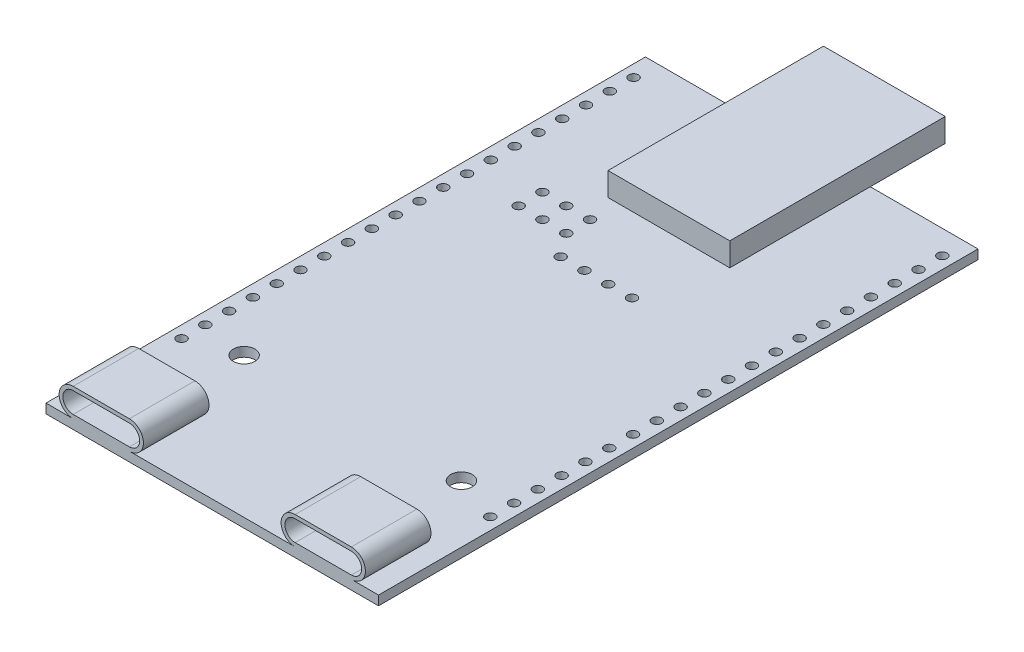
SolidWorks part; units mm, degrees
ref_plane "Piano frontale" through (0, 0, 0) normal (0, 0, 1) x (1, 0, 0)
ref_plane "Piano superiore" through (0, 0, 0) normal (0, 1, 0) x (1, 0, 0)
ref_plane "Piano destro" through (0, 0, 0) normal (1, 0, 0) x (0, 0, -1)
sketch "Schizzo1" plane through (0, 0, 0) normal (0, 1, 0) x (1, 0, 0)
  line L1 (0, 0) -> (-35.5, 0)
  line L2 (0, 0) -> (0, 64)
  line L3 (0, 64) -> (-35.5, 64)
  line L4 (-35.5, 0) -> (-35.5, 64)
  dimension "D1" = 64
  dimension "D2" = 35.5
extrude "Estrusione-Estrusione1" add sketch "Schizzo1" along normal blind 1
sketch "Schizzo2" plane through (0, 1, 0) normal (0, 1, 0) x (1, 0, 0)
  line L0 (0, 64) -> (-35.5, 64) construction
  line L1 (-11.5, 49) -> (-24.5, 49)
  line L2 (-11.5, 49) -> (-11.5, 72)
  line L3 (-11.5, 72) -> (-24.5, 72)
  line L4 (-24.5, 49) -> (-24.5, 72)
  line L5 (-35.5, 64) -> (-35.5, 0) construction
  dimension "D1" = 13
  dimension "D2" = 23
  dimension "D3" = 8
  dimension "D4" = 11
extrude "Estrusione-Estrusione2" add sketch "Schizzo2" along normal blind 2.5
sketch "Schizzo3" plane through (0, 1, 0) normal (0, 1, 0) x (1, 0, 0)
  line L0 (0, 64) -> (-11.5, 64) construction
  line L1 (0, 0) -> (0, 64) construction
  line L2 (-35.5, 64) -> (-35.5, 0) construction
  line L3 (-21.56, 41) -> (-13.94, 41) construction
  line L4 (-35.5, 0) -> (0, 0) construction
  line L5 (-28.5, 43.46) -> (-23.42, 43.46) construction
  line L6 (-23.42, 43.46) -> (-23.42, 46) construction
  line L7 (-23.42, 46) -> (-28.5, 46) construction
  line L8 (-28.5, 46) -> (-28.5, 43.46) construction
  line L9 (-24.5, 64) -> (-35.5, 64) construction
  circle A0 centre (-1.27, 61.46) radius 0.51
  circle A1 centre (-1.27, 58.92) radius 0.51
  circle A2 centre (-1.27, 56.38) radius 0.51
  circle A3 centre (-1.27, 53.84) radius 0.51
  circle A4 centre (-1.27, 51.3) radius 0.51
  circle A5 centre (-1.27, 48.76) radius 0.51
  circle A6 centre (-1.27, 46.22) radius 0.51
  circle A7 centre (-1.27, 43.68) radius 0.51
  circle A8 centre (-1.27, 41.14) radius 0.51
  circle A9 centre (-1.27, 38.6) radius 0.51
  circle A10 centre (-1.27, 36.06) radius 0.51
  circle A11 centre (-1.27, 33.52) radius 0.51
  circle A12 centre (-1.27, 30.98) radius 0.51
  circle A13 centre (-1.27, 28.44) radius 0.51
  circle A14 centre (-1.27, 25.9) radius 0.51
  circle A15 centre (-1.27, 23.36) radius 0.51
  circle A16 centre (-1.27, 20.82) radius 0.51
  circle A17 centre (-1.27, 18.28) radius 0.51
  circle A18 centre (-1.27, 15.74) radius 0.51
  circle A19 centre (-1.27, 13.2) radius 0.51
  circle A20 centre (-34.23, 61.46) radius 0.51
  circle A21 centre (-34.23, 58.92) radius 0.51
  circle A22 centre (-34.23, 56.38) radius 0.51
  circle A23 centre (-34.23, 53.84) radius 0.51
  circle A24 centre (-34.23, 51.3) radius 0.51
  circle A25 centre (-34.23, 48.76) radius 0.51
  circle A26 centre (-34.23, 46.22) radius 0.51
  circle A27 centre (-34.23, 43.68) radius 0.51
  circle A28 centre (-34.23, 41.14) radius 0.51
  circle A29 centre (-34.23, 38.6) radius 0.51
  circle A30 centre (-34.23, 36.06) radius 0.51
  circle A31 centre (-34.23, 33.52) radius 0.51
  circle A32 centre (-34.23, 30.98) radius 0.51
  circle A33 centre (-34.23, 28.44) radius 0.51
  circle A34 centre (-34.23, 25.9) radius 0.51
  circle A35 centre (-34.23, 23.36) radius 0.51
  circle A36 centre (-34.23, 20.82) radius 0.51
  circle A37 centre (-34.23, 18.28) radius 0.51
  circle A38 centre (-34.23, 15.74) radius 0.51
  circle A39 centre (-34.23, 13.2) radius 0.51
  circle A40 centre (-21.56, 41) radius 0.51
  circle A41 centre (-19.02, 41) radius 0.51
  circle A42 centre (-16.48, 41) radius 0.51
  circle A43 centre (-13.94, 41) radius 0.51
  circle A44 centre (-28.5, 46) radius 0.51
  circle A45 centre (-25.96, 46) radius 0.51
  circle A46 centre (-23.42, 46) radius 0.51
  circle A47 centre (-28.5, 43.46) radius 0.51
  circle A48 centre (-25.96, 43.46) radius 0.51
  circle A49 centre (-23.42, 43.46) radius 0.51
  point P108 (-26.9595, 44.1376)
  point P109 (-26.9595, 45.7828)
  dimension "D1" = 1.02
  dimension "D3" = 2.54
  dimension "D4" = 1.27
  dimension "D8" = 2.54
  dimension "D9" = 2.54
  dimension "D10" = 2.54
  dimension "D5" = 2.54
  dimension "D7" = 1.27
  dimension "D11" = 13.94
  dimension "D12" = 41
  dimension "D13" = 2.54
  dimension "D14" = 2.54
  dimension "D15" = 7
  dimension "D16" = 18
  dimension "D2" = 20
  dimension "D6" = 2
extrude "Taglio-Estrusione1" cut sketch "Schizzo3" against normal blind 2.5
sketch "Schizzo6" plane through (0, 0, 0) normal (0, 0, 1) x (1, 0, 0)
  line L0 (-32.6, 2.5) -> (-26.6, 2.5) construction
  line L1 (-32.6, 4) -> (-26.6, 4)
  line L2 (-32.6, 1) -> (-26.6, 1)
  line L3 (-34.1, 2.5) -> (-25.1, 2.5) construction
  line L4 (-35.5, 1) -> (0, 1) construction
  line L5 (-8.9, 2.5) -> (-2.9, 2.5) construction
  line L6 (-8.9, 4) -> (-2.9, 4)
  line L7 (-8.9, 1) -> (-2.9, 1)
  line L8 (0, 1) -> (0, 0) construction
  line L9 (-32.6, 2.5) -> (-26.6, 2.5) construction
  line L10 (-32.6, 3.6) -> (-26.6, 3.6)
  line L11 (-32.6, 1.4) -> (-26.6, 1.4)
  line L12 (-8.9, 2.5) -> (-2.9, 2.5) construction
  line L13 (-8.9, 3.6) -> (-2.9, 3.6)
  line L14 (-8.9, 1.4) -> (-2.9, 1.4)
  arc A0 (-32.6, 4) -> (-32.6, 1) centre (-32.6, 2.5) ccw
  arc A1 (-26.6, 1) -> (-26.6, 4) centre (-26.6, 2.5) ccw
  arc A2 (-8.9, 4) -> (-8.9, 1) centre (-8.9, 2.5) ccw
  arc A3 (-2.9, 1) -> (-2.9, 4) centre (-2.9, 2.5) ccw
  arc A4 (-32.6, 3.6) -> (-32.6, 1.4) centre (-32.6, 2.5) ccw
  arc A5 (-26.6, 1.4) -> (-26.6, 3.6) centre (-26.6, 2.5) ccw
  arc A6 (-8.9, 3.6) -> (-8.9, 1.4) centre (-8.9, 2.5) ccw
  arc A7 (-2.9, 1.4) -> (-2.9, 3.6) centre (-2.9, 2.5) ccw
  point P2 (-29.6, 2.5)
  point P14 (-5.9, 2.5)
  point P19 (-1.4, 2.5)
  point P25 (-29.6, 2.5)
  point P30 (-5.9, 2.5)
  line M21 (0, 1) -> (-35.5, 1)
  dimension "D1" = 9
  dimension "D2" = 3
  dimension "D3" = 1.4
  dimension "D4" = 1.4
  dimension "D5" = 0.4
extrude "Estrusione-Estrusione3" add sketch "Schizzo6" against normal blind 7 contours L11 A5 L10 A4 | A1 L1 A0 A5 L11 A4 L10 M21 | L14 A7 L13 A6 | A3 L6 A2 A7 L14 A6 L13 M21 region at (-10.3051, 2.5, 0) region at (-29.6, 3.9051, 0) region at (-29.6, 2.5, 0) region at (-5.9, 2.5, 0)
extrude "Taglio-Estrusione2" cut sketch "Schizzo6<3>" against normal blind 6 contours L11 A5 L10 A4 | L14 A7 L13 A6 region at (-29.6, 2.5, 0) region at (-5.9, 2.5, 0)
sketch "Schizzo6<3>" plane through (0, 0, 0) normal (0, 0, 1) x (1, 0, 0) same geometry as "Schizzo6"
sketch "Schizzo7" plane through (0, 1, 0) normal (0, 1, 0) x (1, 0, 0)
  line L0 (0, 0) -> (0, 64) construction
  line L1 (-35.5, 64) -> (-35.5, 0) construction
  line L2 (-26.6, 0) -> (-8.9, 0) construction
  circle A0 centre (-29.35, 15) radius 1.15
  circle A1 centre (-6.15, 15) radius 1.15
  dimension "D1" = 2.3
  dimension "D3" = 6.15
  dimension "D4" = 15
  dimension "D5" = 15
  dimension "D2" = 6.15
extrude "Taglio-Estrusione3" cut sketch "Schizzo7" against normal blind 6
